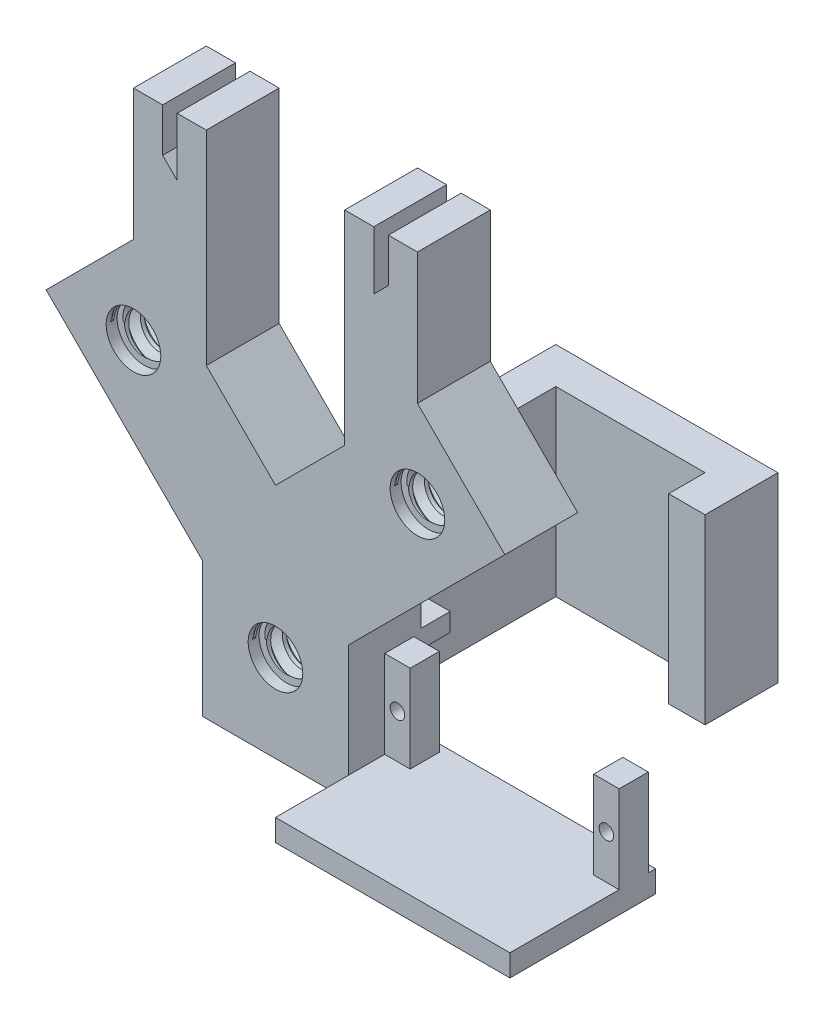
SolidWorks part; units mm, degrees
ref_plane "Front Plane" through (0, 0, 0) normal (0, 0, 1) x (1, 0, 0)
ref_plane "Top Plane" through (0, 0, 0) normal (0, 1, 0) x (1, 0, 0)
ref_plane "Right Plane" through (0, 0, 0) normal (1, 0, 0) x (0, 0, -1)
sketch "Sketch1" plane through (0, 0, 0) normal (0, 0, 1) x (1, 0, 0)
  line L0 (-31.5, 0) -> (-31.5, -80.9035) construction
  line L1 (0, 0) -> (-63, 0)
  line L2 (0, 0) -> (0, -52)
  line L3 (0, -52) -> (-63, -52)
  line L4 (-63, 0) -> (-63, -52)
  line L5 (-63, -12) -> (-51, 0)
  line L6 (-51, 0) -> (-31.5, -19.5)
  line L8 (-21.5, -52) -> (-41.5, -52)
  line L9 (-41.5, -52) -> (-41.5, -33.5)
  line L10 (-41.5, -33.5) -> (-63, -12)
  line L11 (-21.5, -52) -> (-21.5, -33.5)
  line L12 (-12, 0) -> (-31.5, -19.5)
  line L13 (0, -12) -> (-12, 0)
  line L14 (-21.5, -33.5) -> (0, -12)
  circle A0 centre (-51, -12) radius 2.75
  circle A1 centre (-12, -12) radius 2.75
  circle A2 centre (-31.5, -40) radius 2.75
  point P11 (-31.5, -52)
  dimension "D2" = 12
  dimension "D3" = 28
  dimension "D4" = 0
  dimension "D6" = 0
  dimension "D7" = 39
  dimension "D8" = 12
  dimension "D9" = 5.5
  dimension "D10" = 5.5
  dimension "D14" = 12
  dimension "D16" = 10
  dimension "D15" = 12
  dimension "D17" = 5.5
  dimension "D1" = 63
  dimension "D5" = 12
  dimension "D11" = 90
  dimension "D12" = 90
  dimension "D13" = 12
extrude "Boss-Extrude1" add sketch "Sketch1" along normal blind 10 contours L0 L6 L5 L10 L9 L8 A2 A0 | L12 L0 A2 L3 L11 L14 L13 A1 region at (-19.9332, -24.1984, 0) region at (-43.0668, -24.1984, 0)
thread "Thread1" pitch 2.1167 method cut profile "Thread Profile1" start angle 0, offset 0, length 20, pitch 2.1167, diameter 5.5
ref_plane "Plane1" through (-53.75, -12, 10) normal (0, -1, 0) x (-1, 0, 0)
sketch "Thread Profile1" plane through (-53.75, -12, 10) normal (0, -1, 0) x (-1, 0, 0)
  line L0 (0, 0) -> (0, 2.1167) construction
  line L1 (0, 0) -> (1.1457, 0.6615)
  line L2 (1.1457, 0.6615) -> (1.1457, 0.926)
  line L3 (1.1457, 0.926) -> (0, 1.5875)
  line L4 (1.1457, 0.7937) -> (0, 0.7937) construction
  line L11 (0, 0) -> (0, 1.5875)
  point P2 (0, 0)
  dimension "Pitch" = 2.1167
  dimension "Profile_Angle" = 60
  dimension "Profile_Land" = 0.2646
  dimension "Profile_Height" = 1.1457
thread "Thread2" pitch 2.1167 method cut profile "Thread Profile2" start angle 0, offset 0, length 20, pitch 2.1167, diameter 5.5
ref_plane "Plane2" through (-14.75, -12, 10) normal (0, -1, 0) x (-1, 0, 0)
sketch "Thread Profile2" plane through (-14.75, -12, 10) normal (0, -1, 0) x (-1, 0, 0)
  line L0 (0, 0) -> (0, 2.1167) construction
  line L1 (0, 0) -> (1.1457, 0.6615)
  line L2 (1.1457, 0.6615) -> (1.1457, 0.926)
  line L3 (1.1457, 0.926) -> (0, 1.5875)
  line L4 (1.1457, 0.7937) -> (0, 0.7937) construction
  line L11 (0, 0) -> (0, 1.5875)
  point P2 (0, 0)
  dimension "Pitch" = 2.1167
  dimension "Profile_Angle" = 60
  dimension "Profile_Land" = 0.2646
  dimension "Profile_Height" = 1.1457
thread "Thread3" pitch 2.1167 method cut profile "Thread Profile3" start angle 0, offset 0, length 20, pitch 2.1167, diameter 5.5
ref_plane "Plane3" through (-34.25, -40, 10) normal (0, -1, 0) x (-1, 0, 0)
sketch "Thread Profile3" plane through (-34.25, -40, 10) normal (0, -1, 0) x (-1, 0, 0)
  line L0 (0, 0) -> (0, 2.1167) construction
  line L1 (0, 0) -> (1.1457, 0.6615)
  line L2 (1.1457, 0.6615) -> (1.1457, 0.926)
  line L3 (1.1457, 0.926) -> (0, 1.5875)
  line L4 (1.1457, 0.7937) -> (0, 0.7937) construction
  line L11 (0, 0) -> (0, 1.5875)
  point P2 (0, 0)
  dimension "Pitch" = 2.1167
  dimension "Profile_Angle" = 60
  dimension "Profile_Land" = 0.2646
  dimension "Profile_Height" = 1.1457
sketch "Sketch8" plane through (0, 0, 10) normal (0, 0, 1) x (1, 0, 0)
  circle A0 centre (-51, -12) radius 3.75
  circle A1 centre (-12, -12) radius 3.75
  circle A2 centre (-31.5, -40) radius 3.75
  dimension "D1" = 7.5
  dimension "D2" = 7.5
  dimension "D3" = 7.5
extrude "Cut-Extrude2" cut sketch "Sketch8" against normal blind 1.5
sketch "Sketch9" plane through (-21.5, 0, 0) normal (1, 0, 0) x (0, 0, -1)
  line L1 (0, -52) -> (-20, -52)
  line L2 (0, -52) -> (0, -49)
  line L3 (0, -49) -> (-20, -49)
  line L4 (-20, -52) -> (-20, -49)
  line L5 (-10, -52) -> (-10, -33.5) construction
  dimension "D1" = 3
  dimension "D2" = 10
extrude "Boss-Extrude3" add sketch "Sketch9" along normal blind 32.2
sketch "Sketch10" plane through (0, -49, 0) normal (0, 1, 0) x (1, 0, 0)
  line L0 (-21.5, 0) -> (-21.5, -10) construction
  line L1 (-21.5, -1) -> (-18, -1)
  line L2 (-21.5, -1) -> (-21.5, -5)
  line L3 (-21.5, -5) -> (-18, -5)
  line L4 (-18, -1) -> (-18, -5)
  line L5 (-5.4, -20) -> (-5.4, 7.6272) construction
  line L6 (10.7, -20) -> (-21.5, -20) construction
  line L7 (10.7, 0) -> (-21.5, 0) construction
  line L8 (10.7, -5) -> (7.2, -5)
  line L9 (7.2, -1) -> (7.2, -5)
  line L10 (10.7, -1) -> (7.2, -1)
  line L11 (10.7, -1) -> (10.7, -5)
  dimension "D1" = 4
  dimension "D2" = 1
  dimension "D3" = 3.5
extrude "Boss-Extrude4" add sketch "Sketch10" along normal blind 12
sketch "Sketch11" plane through (0, 0, 1) normal (0, 0, -1) x (-1, 0, 0)
  line L0 (18, -37) -> (18, -49) construction
  line L1 (-7.2, -37) -> (-7.2, -49) construction
  line L2 (18, -37) -> (21.5, -37) construction
  line L3 (-10.7, -37) -> (-7.2, -37) construction
  circle A0 centre (-8.95, -43) radius 1
  circle A1 centre (19.75, -43) radius 1
  point P6 (18, -43)
  point P9 (-7.2, -43)
  point P12 (19.75, -37)
  point P15 (-8.95, -37)
  dimension "D1" = 0
  dimension "D2" = 0
  dimension "D3" = 2
  dimension "D4" = 2
  dimension "D5" = 0
  dimension "D6" = 0
extrude "Cut-Extrude3" cut sketch "Sketch11" against normal blind 22
sketch "Sketch13" plane through (0, -52, 0) normal (0, -1, 0) x (-1, 0, 0)
  line L0 (36.5, 0) -> (36.5, 33.5)
  line L1 (36.5, 33.5) -> (6, 33.5)
  line L2 (6, 33.5) -> (6, 23.5)
  line L3 (6, 23.5) -> (11, 23.5)
  line L4 (11, 23.5) -> (11, 28.5)
  line L5 (11, 28.5) -> (31.5, 28.5)
  line L6 (31.5, 28.5) -> (31.5, 0)
  line L7 (-10.7, 0) -> (41.5, 0) construction
  line L8 (31.5, 0) -> (36.5, 0)
  dimension "D1" = 10
  dimension "D2" = 5
  dimension "D3" = 28.5
  dimension "D4" = 20.5
  dimension "D5" = 5
  dimension "D6" = 10
  dimension "D7" = 5
extrude "Boss-Extrude5" add sketch "Sketch13" against normal blind 25
sketch "Sketch14" plane through (0, 0, 0) normal (0, 0, -1) x (-1, 0, 0)
  line L0 (21.5, -49) -> (21.5, -33.5) construction
  line L1 (21.5, -39) -> (31.5, -39)
  line L2 (21.5, -39) -> (21.5, -36.5)
  line L3 (21.5, -36.5) -> (31.5, -36.5)
  line L4 (31.5, -39) -> (31.5, -36.5)
  line L5 (31.5, -42.75) -> (31.5, -52) construction
  line L6 (-10.7, -49) -> (21.5, -49) construction
  dimension "D1" = 2.5
  dimension "D2" = 10
extrude "Boss-Extrude6" add sketch "Sketch14" along normal blind 4
sketch "Sketch15" plane through (0, 0, 0) normal (0, 0, -1) x (-1, 0, 0)
  line L0 (41.5, -52) -> (41.5, -33.5) construction
  line L1 (41.5, -36) -> (39, -36)
  line L2 (41.5, -36) -> (41.5, -39)
  line L3 (41.5, -39) -> (39, -39)
  line L4 (39, -36) -> (39, -39)
  line L6 (36.5, -52) -> (41.5, -52) construction
  line L7 (36.5, -27) -> (36.5, -52) construction
  dimension "D1" = 13
  dimension "D2" = 3
  dimension "D3" = 2.5
extrude "Boss-Extrude7" add sketch "Sketch15" along normal blind 7
sketch "Sketch16" plane through (0, -39, 0) normal (0, -1, 0) x (-1, 0, 0)
  line L1 (41.5, 7) -> (39, 7)
  line L2 (41.5, 7) -> (41.5, 3.5)
  line L3 (41.5, 3.5) -> (39, 3.5)
  line L4 (39, 7) -> (39, 3.5)
  line L5 (39, 7) -> (41.5, 7) construction
  line L6 (39, 7) -> (39, 0) construction
  line L7 (41.5, 7) -> (41.5, 0) construction
  dimension "D1" = 0
  dimension "D2" = 3.5
  dimension "D3" = 0
  dimension "D4" = 0
  dimension "D5" = 90
extrude "Boss-Extrude8" add sketch "Sketch16" along normal up to vertex (13 mm away) up to point (-36.5, -52, 0)
sketch "Sketch18" plane through (0, 0, 10) normal (0, 0, 1) x (1, 0, 0)
  line L0 (-12, 0) -> (-22, -10)
  line L1 (-12, 0) -> (-31.5, -19.5) construction
  line L2 (-22, -10) -> (-22, 18)
  line L3 (-22, 18) -> (-12, 18)
  line L4 (-12, 18) -> (-12, 0)
  line L5 (-31.5, -19.5) -> (-31.5, -67.4858) construction
  line L6 (-41, 18) -> (-51, 18)
  line L7 (-41, -10) -> (-41, 18)
  line L8 (-51, 0) -> (-41, -10)
  line L9 (-51, 18) -> (-51, 0)
  dimension "D1" = 10
  dimension "D2" = 18
extrude "Boss-Extrude9" add sketch "Sketch18" against normal up to vertex (10 mm away) up to point (-12, 0, 0)
sketch "Sketch19" plane through (0, 18, 0) normal (0, 1, 0) x (1, 0, 0)
  line L0 (-12, 0) -> (-22, 0) construction
  line L1 (-16, 0) -> (-18, 0)
  line L2 (-16, 0) -> (-16, -10)
  line L3 (-16, -10) -> (-18, -10)
  line L4 (-18, 0) -> (-18, -10)
  line L5 (-12, -10) -> (-22, -10) construction
  line L6 (-41, 0) -> (-51, 0) construction
  line L7 (-45, 0) -> (-47, 0)
  line L8 (-45, 0) -> (-45, -10)
  line L9 (-45, -10) -> (-47, -10)
  line L10 (-47, 0) -> (-47, -10)
  line L11 (-41, -10) -> (-51, -10) construction
  point P16 (-17, 0)
  point P17 (-17, 0)
  point P18 (-46, 0)
  point P19 (-46, 0)
  dimension "D1" = 2
  dimension "D2" = 0
  dimension "D3" = 2
  dimension "D4" = 0
extrude "Cut-Extrude4" cut sketch "Sketch19" against normal blind 8
sketch "Sketch20" plane through (0, 0, 10) normal (0, 0, 1) x (1, 0, 0)
  line L4 (-31.5, -19.5) -> (-31.5, 35.3156) construction
  line L5 (-18, 10) -> (-16, 10)
  line L6 (-16, 10) -> (-16, 12)
  line L7 (-16, 10) -> (-16, 18) construction
  line L8 (-16, 12) -> (-18, 10)
  line L9 (-47, 10) -> (-47, 12)
  line L10 (-45, 10) -> (-47, 10)
  line L11 (-47, 12) -> (-45, 10)
  dimension "D1" = 2
extrude "Boss-Extrude10" add sketch "Sketch20" against normal up to vertex (10 mm away) up to point (-18, 10, 0)
